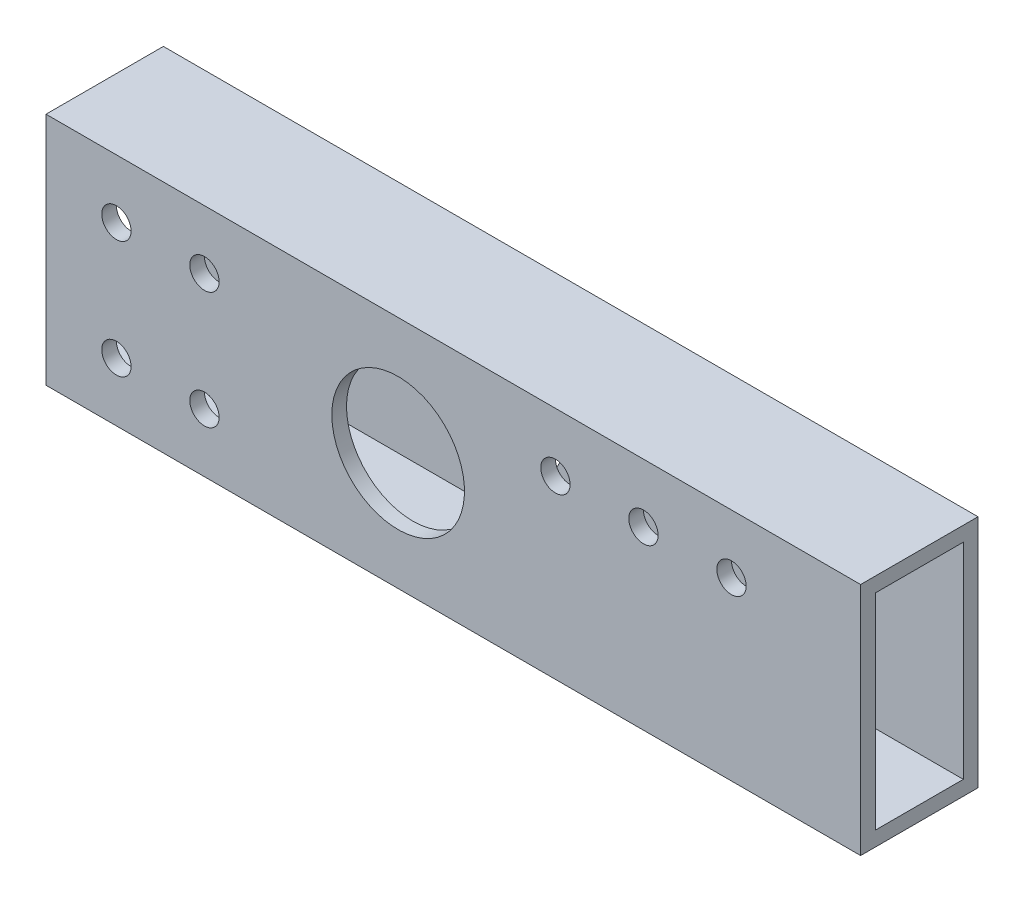
SolidWorks part; units mm, degrees
ref_plane "Front Plane" through (0, 0, 0) normal (0, 0, 1) x (1, 0, 0)
ref_plane "Top Plane" through (0, 0, 0) normal (0, 1, 0) x (1, 0, 0)
ref_plane "Right Plane" through (0, 0, 0) normal (1, 0, 0) x (0, 0, -1)
sketch "Sketch1" plane through (0, 0, 0) normal (0, 1, 0) x (1, 0, 0)
  line L1 (0, 0) -> (176.276, 0)
  line L2 (0, 0) -> (0, 25.4)
  line L3 (0, 25.4) -> (176.276, 25.4)
  line L4 (176.276, 0) -> (176.276, 25.4)
  dimension "D1" = 176.276
  dimension "D2" = 25.4
extrude "Boss-Extrude1" add sketch "Sketch1" along normal blind 50.8
sketch "Sketch2" plane through (176.276, 0, 0) normal (1, 0, 0) x (0, 0, -1)
  line L0 (3.175, 47.625) -> (3.175, 3.175)
  line L1 (0, 50.8) -> (25.4, 50.8)
  line L2 (0, 50.8) -> (0, 0)
  line L3 (0, 0) -> (25.4, 0)
  line L4 (25.4, 50.8) -> (25.4, 0)
  line L5 (3.175, 3.175) -> (22.225, 3.175)
  line L6 (22.225, 47.625) -> (22.225, 3.175)
  line L7 (3.175, 47.625) -> (22.225, 47.625)
  dimension "D1" = 3.175
extrude "Cut-Extrude1" cut sketch "Sketch2" against normal through all flip side to cut
sketch "Sketch3" plane through (0, 0, -25.4) normal (0, 0, -1) x (-1, 0, 0)
  line L1 (-176.276, 50.8) -> (0, 50.8) construction
  line L2 (0, 50.8) -> (0, 0) construction
  circle A0 centre (-76.2, 25.4) radius 14.351
  dimension "D1" = 28.702
  dimension "D4" = 76.2
  dimension "D3" = 25.4
extrude "Cut-Extrude2" cut sketch "Sketch3" against normal through all
sketch "Sketch4" plane through (0, 0, 0) normal (0, 0, 1) x (1, 0, 0)
  line L0 (176.276, 50.8) -> (176.276, 0) construction
  line L2 (0, 50.8) -> (176.276, 50.8) construction
  circle A0 centre (148.336, 38.1) radius 3.175
  circle A1 centre (129.286, 38.1) radius 3.175
  circle A2 centre (110.236, 38.1) radius 3.175
  dimension "D1" = 6.35
  dimension "D2" = 6.35
  dimension "D3" = 6.35
  dimension "D4" = 27.94
  dimension "D5" = 19.05
  dimension "D6" = 19.05
  dimension "D7" = 12.7
  dimension "D8" = 12.7
  dimension "D9" = 12.7
extrude "Cut-Extrude3" cut sketch "Sketch4" against normal through all
sketch "Sketch5" plane through (0, 0, 0) normal (0, 0, 1) x (1, 0, 0)
  line L0 (0, 50.8) -> (0, 0) construction
  line L1 (0, 0) -> (176.276, 0) construction
  line L2 (0, 50.8) -> (176.276, 50.8) construction
  circle A0 centre (15.24, 38.1) radius 3.175
  circle A1 centre (15.24, 12.7) radius 3.175
  circle A2 centre (34.29, 12.7) radius 3.175
  circle A3 centre (34.29, 38.1) radius 3.175
  dimension "D5" = 6.35
  dimension "D6" = 6.35
  dimension "D7" = 6.35
  dimension "D8" = 6.35
  dimension "D1" = 15.24
  dimension "D2" = 19.05
  dimension "D3" = 15.24
  dimension "D4" = 19.05
  dimension "D9" = 12.7
  dimension "D10" = 12.7
  dimension "D11" = 12.7
  dimension "D12" = 12.7
extrude "Cut-Extrude4" cut sketch "Sketch5" against normal through all
